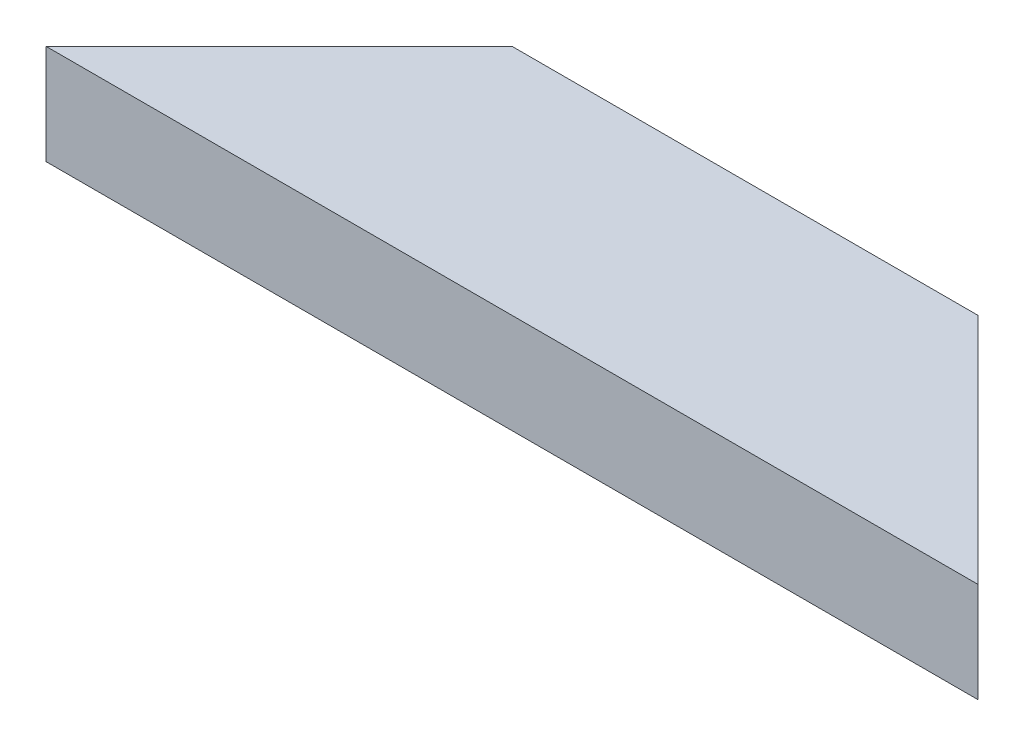
SolidWorks part; units mm, degrees
material "Pine"
ref_plane "Front Plane" through (0, 0, 0) normal (0, 0, 1) x (1, 0, 0)
ref_plane "Top Plane" through (0, 0, 0) normal (0, 1, 0) x (1, 0, 0)
ref_plane "Right Plane" through (0, 0, 0) normal (1, 0, 0) x (0, 0, -1)
sketch "Sketch1" plane through (0, 0, 0) normal (0, 1, 0) x (1, 0, 0)
  line L0 (-106.0606, 52.9788) -> (71.7394, 52.9788)
  line L1 (71.7394, 52.9788) -> (160.6394, -35.9212)
  line L3 (-106.0606, 52.9788) -> (-194.9606, -35.9212)
  line L4 (-17.1606, 52.9788) -> (-17.1606, -35.9212)
  line L5 (-194.9606, -35.9212) -> (160.6394, -35.9212)
  line L8 (-106.0606, -35.9212) -> (71.7394, -35.9212) construction
  dimension "D1" = 45
  dimension "D2" = 45
extrude "Boss-Extrude1" add sketch "Sketch1" along normal blind 38.1 contours L3 L5 L1 L0
